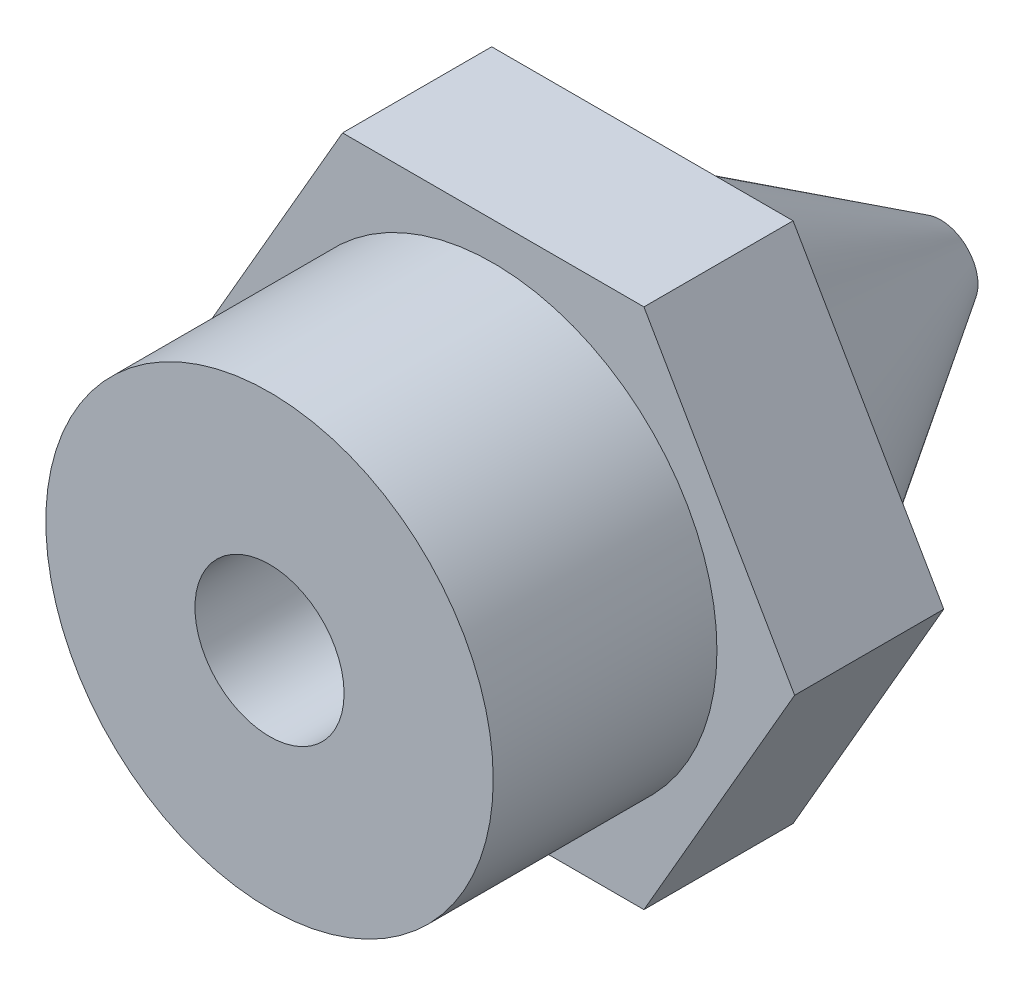
SolidWorks part; units mm, degrees
material "Laiton"
ref_plane "Plan de face" through (0, 0, 0) normal (0, 0, 1) x (1, 0, 0)
ref_plane "Plan de dessus" through (0, 0, 0) normal (0, 1, 0) x (1, 0, 0)
ref_plane "Plan de droite" through (0, 0, 0) normal (1, 0, 0) x (0, 0, -1)
sketch "Esquisse1" plane through (0, 0, 0) normal (0, 0, 1) x (1, 0, 0)
  line L1 (4.0415, 0) -> (2.0207, 3.5)
  line L2 (2.0207, 3.5) -> (-2.0207, 3.5)
  line L3 (-2.0207, 3.5) -> (-4.0415, 0)
  line L4 (-4.0415, 0) -> (-2.0207, -3.5)
  line L5 (-2.0207, -3.5) -> (2.0207, -3.5)
  line L6 (2.0207, -3.5) -> (4.0415, 0)
  circle A0 centre (0, 0) radius 3.5 construction
  dimension "D1" = 7
extrude "Boss.-Extru.1" add sketch "Esquisse1" along normal blind 9 contours L3 L4 L5 L6 L1 L2
sketch "Esquisse2" plane through (0, 0, 9) normal (0, 0, 1) x (1, 0, 0)
  line L1 (-9.4849, 6.2226) -> (10.1391, 6.2226)
  line L2 (-9.4849, 6.2226) -> (-9.4849, -9.3115)
  line L3 (-9.4849, -9.3115) -> (10.1391, -9.3115)
  line L4 (10.1391, 6.2226) -> (10.1391, -9.3115)
  circle A0 centre (0, 0) radius 3
  dimension "D1" = 6
extrude "Enlèv. mat.-Extru.1" cut sketch "Esquisse2" against normal blind 3
cosmetic thread "Représentation de filetage1" parameters "D1"=3, "D2"=4.891
sketch "Esquisse3" plane through (0, 0, 0) normal (0, 0, -1) x (-1, 0, 0)
  line L1 (5.6434, -6.9413) -> (-5.6238, -6.9413)
  line L2 (5.6434, -6.9413) -> (5.6434, 7.0198)
  line L3 (5.6434, 7.0198) -> (-5.6238, 7.0198)
  line L4 (-5.6238, -6.9413) -> (-5.6238, 7.0198)
  circle A0 centre (0, 0) radius 3
  dimension "D1" = 6
extrude "Enlèv. mat.-Extru.2" cut sketch "Esquisse3" against normal blind 4
chamfer "Chanfrein1" distance 4 angle 32 1 edges at (-3, 0, 0) first distance on face at (-3, 0, 4)
sketch "Esquisse4" plane through (0, 0, 0) normal (0, 1, 0) x (1, 0, 0)
  line L0 (0, -10.3816) -> (0, 2.1166) construction
  line L1 (0, -9) -> (1, -9)
  line L2 (-3, -9) -> (3, -9) construction
  line L3 (0, 0) -> (0.25, 0)
  line L4 (0.25, 0) -> (1, -6.1083)
  line L5 (0, -9) -> (0, 0)
  line L9 (1, -6.1083) -> (1, -9)
  dimension "D1" = 1
  dimension "D2" = 0.25
  dimension "D3" = 7
  dimension "D4" = 2.8917
revolve "Enlèvement de matière-Révolution1" cut sketch "Esquisse4" angle 360 about L0
